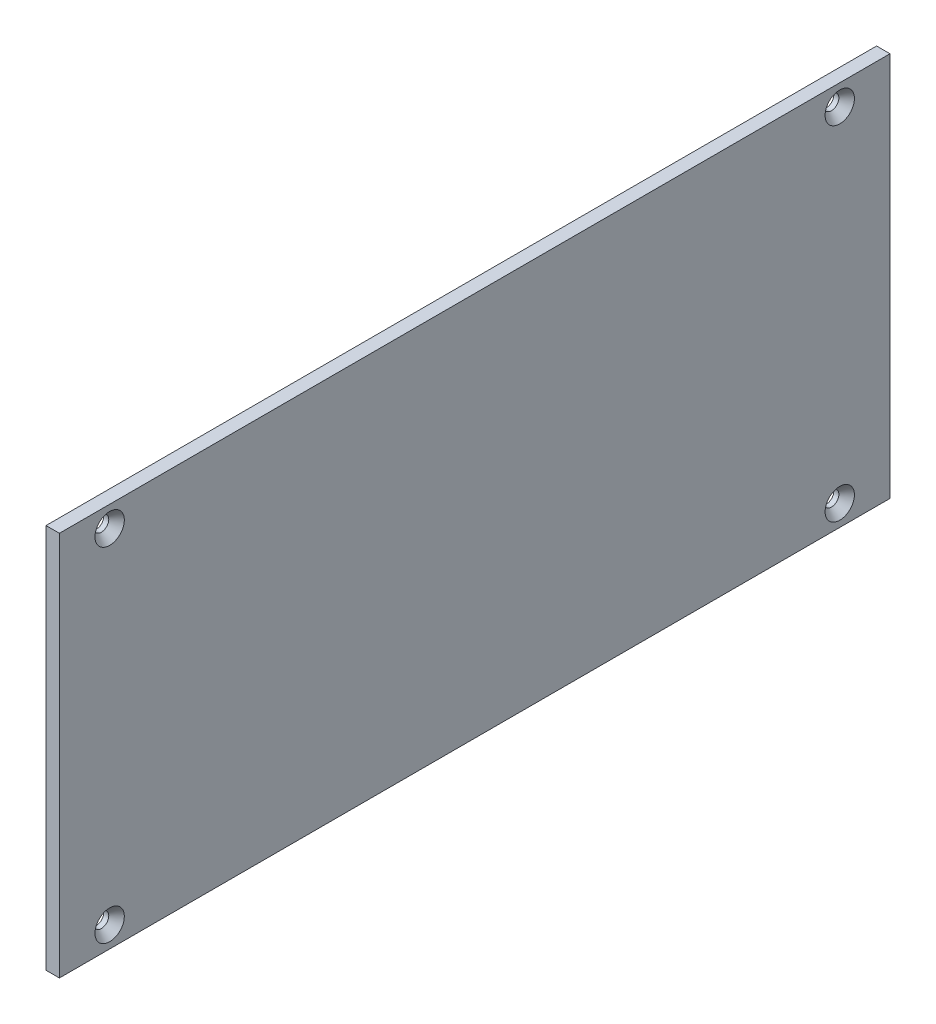
SolidWorks part; units mm, degrees
material "6061-T4 (SS)"
ref_plane "Front Plane" through (0, 0, 0) normal (0, 0, 1) x (1, 0, 0)
ref_plane "Top Plane" through (0, 0, 0) normal (0, 1, 0) x (1, 0, 0)
ref_plane "Right Plane" through (0, 0, 0) normal (1, 0, 0) x (0, 0, -1)
sketch "Sketch1" plane through (0, 0, 0) normal (1, 0, 0) x (0, 0, -1)
  line L1 (0, 0) -> (99.2004, 0)
  line L2 (0, 0) -> (0, 46)
  line L3 (0, 46) -> (99.2004, 46)
  line L4 (99.2004, 0) -> (99.2004, 46)
  dimension "D1" = 46
  dimension "D2" = 99.2004
extrude "Boss-Extrude1" add sketch "Sketch1" along normal blind 1.6002
hole_wizard "CSK for #0 Flat Head Socket Cap Screw1" positions "Sketch3" profile "Sketch4" countersink size "#0" standard "ANSI Inch" end condition through all
sketch "Sketch3" plane through (1.6002, 0, 0) normal (1, 0, 0) x (0, 0, -1)
  line L0 (6, 43.5) -> (6, 2.5) construction
  line L1 (6, 2.5) -> (93.2004, 2.5) construction
  line L2 (93.2004, 2.5) -> (93.2004, 43.5) construction
  line L3 (93.2004, 43.5) -> (6, 43.5) construction
  line L5 (0, 23) -> (6, 23) construction
  line L6 (0, 46) -> (0, 0) construction
  line L7 (6, 23) -> (93.2004, 23) construction
  line L8 (93.2004, 23) -> (99.2004, 23) construction
  line L9 (99.2004, 0) -> (99.2004, 46) construction
  line L11 (99.2004, 46) -> (0, 46) construction
  line L12 (0, 0) -> (99.2004, 0) construction
  point P0 (6, 43.5)
  point P2 (6, 2.5)
  point P4 (93.2004, 2.5)
  point P6 (93.2004, 43.5)
  dimension "D1" = 6
  dimension "D2" = 2.5
  dimension "D3" = 2.5
  dimension "D4" = 6
sketch "Sketch4" plane through (1.6002, 43.5, -6) normal (0, 1, 0) x (0, 0, -1)
  line L0 (0, 0) -> (0, 1.6002)
  line L1 (0, 1.6002) -> (0.889, 1.6002)
  line L2 (0.889, 1.6002) -> (0.889, 0.9935)
  line L3 (0.889, 0.9935) -> (1.7526, 0)
  line L5 (1.7526, 0) -> (0, 0)
  line L6 (-0.889, 0.9935) -> (-1.7526, 0) construction
  line L11 (0, -6.35) -> (0, 107.95) construction
  dimension "Thru Hole Dia." = 1.778
  dimension "Thru Hole Depth" = 1.6002
  dimension "Near C'Sink Dia." = 3.5052
  dimension "Near C'Sink Angle" = 82
